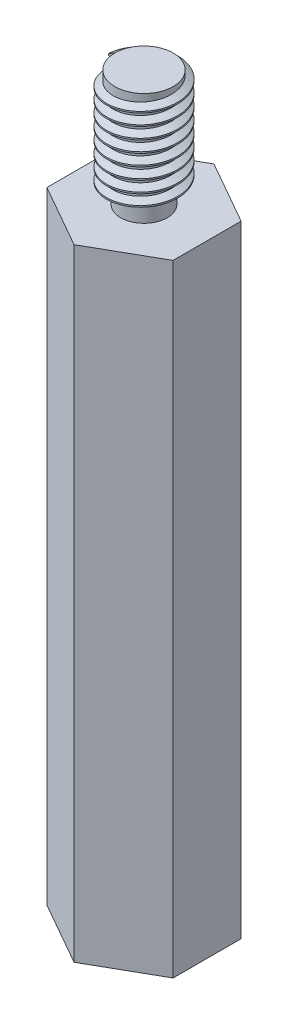
SolidWorks part; units mm, degrees
material "1.4000 (X6Cr13)"
ref_plane "Plan de face" through (0, 0, 0) normal (0, 0, 1) x (1, 0, 0)
ref_plane "Plan de dessus" through (0, 0, 0) normal (0, 1, 0) x (1, 0, 0)
ref_plane "Plan de droite" through (0, 0, 0) normal (1, 0, 0) x (0, 0, -1)
sketch "Esquisse1" plane through (0, 0, 0) normal (0, 1, 0) x (1, 0, 0)
  line L0 (-3.25, 0) -> (3.25, 0) construction
  line L1 (0, 3.6) -> (0, -3.6) construction
  line L2 (-3.25, 1.75) -> (-3.25, -1.75)
  line L3 (0, 3.6) -> (-3.25, 1.75)
  line L4 (-3.25, -1.75) -> (0, -3.6)
  line L5 (3.25, -1.75) -> (0, -3.6)
  line L6 (0, 3.6) -> (3.25, 1.75)
  line L7 (3.25, 1.75) -> (3.25, -1.75)
  point P2 (0, 0)
  point P6 (0, 0)
  point P9 (-3.25, 0)
  dimension "D1" = 6.5
  dimension "D2" = 7.2
  dimension "D3" = 3.5
extrude "Boss.-Extru.1" add sketch "Esquisse1" along normal blind 32
sketch "Esquisse2" plane through (0, 0, 0) normal (0, -1, 0) x (1, 0, 0)
  circle A0 centre (0, 0) radius 1.5
  dimension "D1" = 3
extrude "Enlèv. mat.-Extru.1" cut sketch "Esquisse2" against normal blind 6
sketch "Esquisse3" plane through (0, 32, 0) normal (0, 1, 0) x (1, 0, 0)
  circle A0 centre (0, 0) radius 1.2
  dimension "D1" = 2.4
extrude "Boss.-Extru.2" add sketch "Esquisse3" along normal blind 6
thread "Filetage2" pitch 0.3175 method extrude profile "Profil de filetage4" start angle 0, offset 0, length 5, pitch 0.3175, diameter 3
ref_plane "Plan4" through (1.5, 0, 0) normal (0, 0, 1) x (1, 0, 0)
sketch "Profil de filetage4" plane through (1.5, 0, 0) normal (0, 0, 1) x (1, 0, 0)
  line L0 (0, 0) -> (0, 0.3175) construction
  line L11 (0, 0) -> (0, 0.2778)
  line L12 (0, 0.2778) -> (-0.1719, 0.1786)
  line L13 (-0.1719, 0.1786) -> (-0.1719, 0.0992)
  line L15 (-0.1719, 0.0992) -> (0, 0)
  line L17 (-0.1719, 0.1389) -> (0, 0.1389) construction
  point P2 (0, 0)
  dimension "Pitch" = 0.3175
  dimension "Profile_Angle" = 60
  dimension "Profile_Land" = 0.0794
  dimension "Profile_Height" = 0.1719
sketch "Esquisse17" plane through (0, 38, 0) normal (0, 1, 0) x (1, 0, 0)
  circle A0 centre (0, 0) radius 1.5
  dimension "D1" = 3
extrude "Boss.-Extru.3" add sketch "Esquisse17" against normal blind 5
thread "Filetage4" pitch 0.6 method extrude profile "Profil de filetage6" start angle 0, offset 0, length 5, pitch 0.6, diameter 3
ref_plane "Plan6" through (-1.5, 38, 0) normal (0, 0, 1) x (-1, 0, 0)
sketch "Profil de filetage6" plane through (-1.5, 38, 0) normal (0, 0, 1) x (-1, 0, 0)
  line L0 (0, 0) -> (0, 0.6) construction
  line L1 (0, 0) -> (0.3248, 0.1875)
  line L2 (0.3248, 0.1875) -> (0.3248, 0.2625)
  line L3 (0.3248, 0.2625) -> (0, 0.45)
  line L4 (0.3248, 0.225) -> (0, 0.225) construction
  line L11 (0, 0) -> (0, 0.45)
  point P2 (0, 0)
  dimension "Pitch" = 0.6
  dimension "Profile_Angle" = 60
  dimension "Profile_Land" = 0.075
  dimension "Profile_Height" = 0.3248
